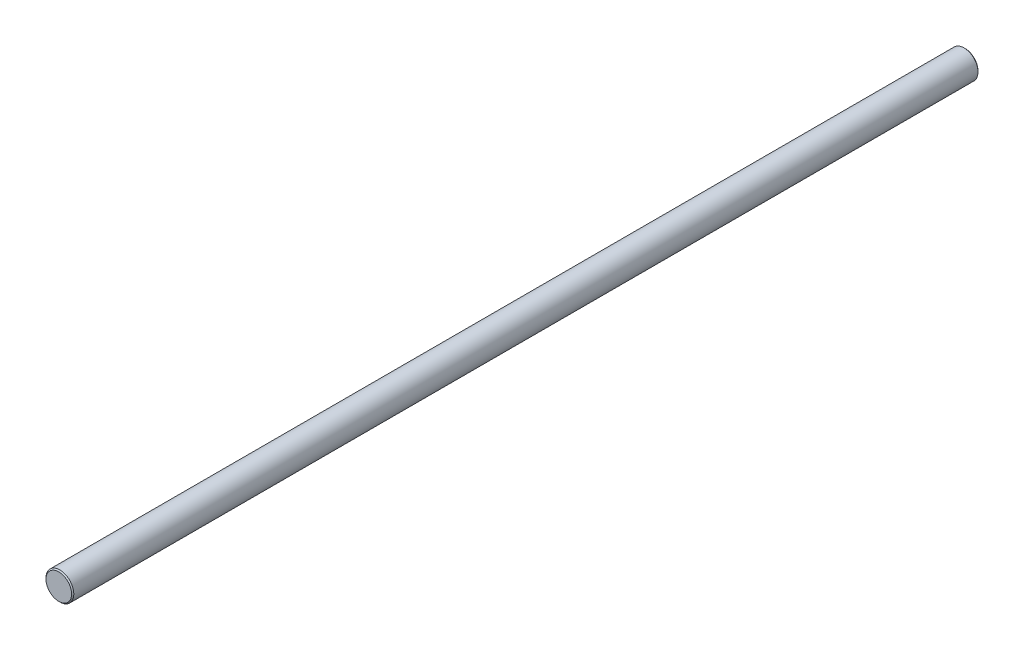
SolidWorks part; units mm, degrees
material "AISI 304"
ref_plane "Спереди" through (0, 0, 0) normal (0, 0, 1) x (1, 0, 0)
ref_plane "Сверху" through (0, 0, 0) normal (0, 1, 0) x (1, 0, 0)
ref_plane "Справа" through (0, 0, 0) normal (1, 0, 0) x (0, 0, -1)
ref_axis "ОсьX" through (-88.99, 0, 0) along (1, 0, 0)
ref_axis "ОсьZ" through (0, 55, 0) along (0, -1, 0)
ref_axis "ОсьY" through (0, 0, -88.99) along (0, 0, 1)
sketch "Эскиз1" plane through (0, 0, 0) normal (0, 0, 1) x (1, 0, 0)
  circle A0 centre (0, 0) radius 12.5
  dimension "D1" = 25
extrude "Бобышка-Вытянуть1" add sketch "Эскиз1" along normal mid plane 814
chamfer "Фаска1" distance 1 angle 45 2 edges at (12.5, 0, -407) (12.5, 0, 407)
